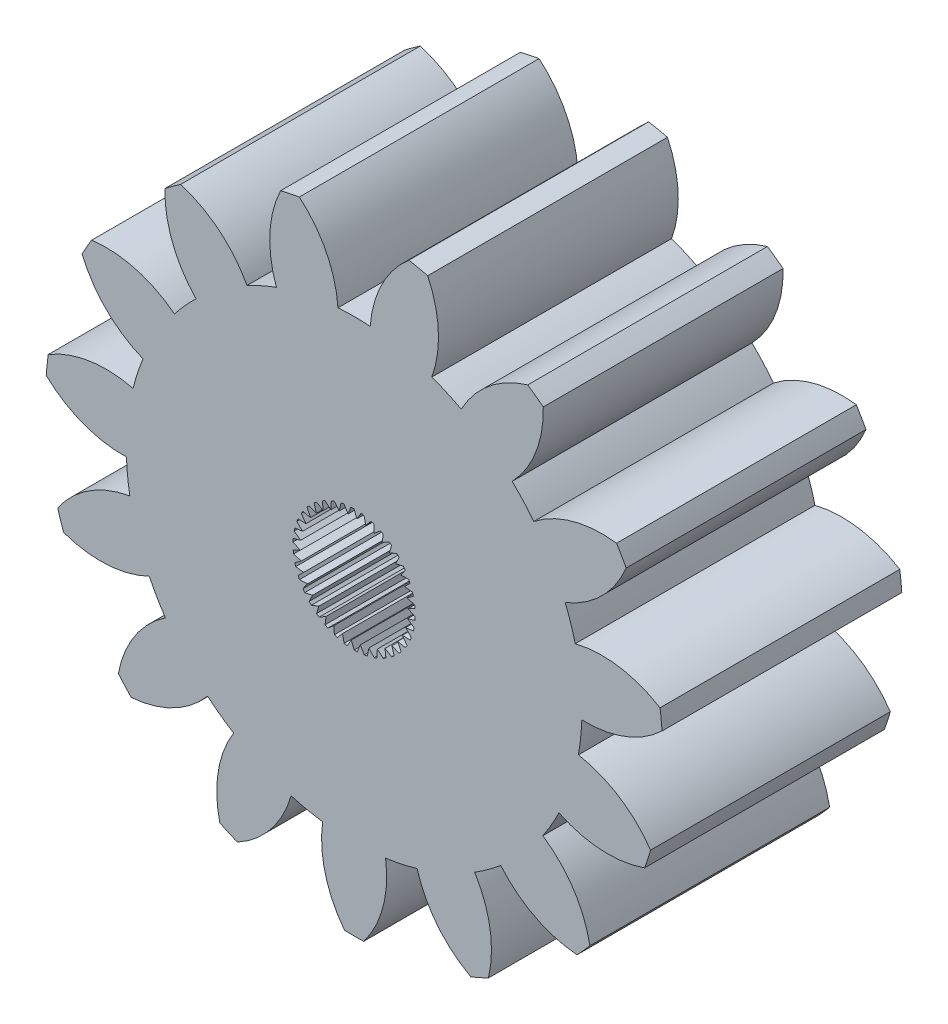
SolidWorks part; units mm, degrees
ref_plane "Front Plane" through (0, 0, 0) normal (0, 0, 1) x (1, 0, 0)
ref_plane "Top Plane" through (0, 0, 0) normal (0, 1, 0) x (1, 0, 0)
ref_plane "Right Plane" through (0, 0, 0) normal (1, 0, 0) x (0, 0, -1)
sketch "Sketch1" plane through (0, 0, 0) normal (0, 0, 1) x (1, 0, 0)
  circle A0 centre (0, 0) radius 70.548
extrude "Boss-Extrude1" add sketch "Sketch1" along normal blind 10
extrude "Cut-Extrude2" cut sketch "Sketch3" against normal through all contours A481 | A60 A239 A238 A237 A236 A235 A234 A233 A232 A231 A230 A229 A228 A227 A226 A225 A224 A223 A222 A221 A220 A219 A218 A217 A216 A215 A214 A213 A212 A211 A210 A209 A208 A207 A206 A205 A204 A203 A202 A201 A200 A199 A198 A197 A196 A195 A194 A193 A192 A191 region at (-345.5536, 6.387, 105.5946) region at (11.564, 6.387, 105.5946)
sketch "Sketch3" plane through (55.0256, -141.7184, 105.5946) normal (0, 0, 1) x (1, 0, 0)
  circle A60 centre (-43.4616, 148.1054) radius 367.5124
  arc A180 (-36.2212, 158.754) -> (-38.993, 156.4899) centre (-34.9077, 154.3174) ccw
  arc A181 (-38.993, 156.4899) -> (-40.2207, 157.0366) centre (-43.4616, 148.1054) ccw
  arc A182 (-40.2207, 157.0366) -> (-40.3928, 160.6114) centre (-44.5688, 158.6188) ccw
  arc A183 (-40.3928, 160.6114) -> (-41.1784, 160.7783) centre (-43.4616, 148.1054) ccw
  arc A184 (-41.1784, 160.7783) -> (-42.7896, 157.5826) centre (-38.1739, 157.2595) ccw
  arc A185 (-42.7896, 157.5826) -> (-44.1336, 157.5826) centre (-43.4616, 148.1054) ccw
  arc A186 (-44.1336, 157.5826) -> (-45.7448, 160.7783) centre (-48.7493, 157.2595) ccw
  arc A187 (-45.7448, 160.7783) -> (-46.5303, 160.6114) centre (-43.4616, 148.1054) ccw
  arc A188 (-46.5303, 160.6114) -> (-46.7024, 157.0366) centre (-42.3544, 158.6188) ccw
  arc A189 (-46.7024, 157.0366) -> (-47.9302, 156.4899) centre (-43.4616, 148.1054) ccw
  arc A190 (-47.9302, 156.4899) -> (-50.702, 158.754) centre (-52.0154, 154.3174) ccw
  arc A191 (-50.702, 158.754) -> (-51.3517, 158.282) centre (-43.4616, 148.1054) ccw
  arc A192 (-51.3517, 158.282) -> (-50.0549, 154.9462) centre (-46.7263, 158.1602) ccw
  arc A193 (-50.0549, 154.9462) -> (-50.9542, 153.9475) centre (-43.4616, 148.1054) ccw
  arc A194 (-50.9542, 153.9475) -> (-54.4072, 154.8885) centre (-53.8026, 150.3012) ccw
  arc A195 (-54.4072, 154.8885) -> (-54.8087, 154.193) centre (-43.4616, 148.1054) ccw
  arc A196 (-54.8087, 154.193) -> (-52.2673, 151.6731) centre (-50.5337, 155.963) ccw
  arc A197 (-52.2673, 151.6731) -> (-52.6826, 150.3949) centre (-43.4616, 148.1054) ccw
  arc A198 (-52.6826, 150.3949) -> (-56.2198, 149.8501) centre (-53.8016, 145.9053) ccw
  arc A199 (-56.2198, 149.8501) -> (-56.3038, 149.0514) centre (-43.4616, 148.1054) ccw
  arc A200 (-56.3038, 149.0514) -> (-52.9571, 147.783) centre (-53.1183, 152.4072) ccw
  arc A201 (-52.9571, 147.783) -> (-52.8166, 146.4464) centre (-43.4616, 148.1054) ccw
  arc A202 (-52.8166, 146.4464) -> (-55.8265, 144.51) centre (-52.0128, 141.8898) ccw
  arc A203 (-55.8265, 144.51) -> (-55.5783, 143.7462) centre (-43.4616, 148.1054) ccw
  arc A204 (-55.5783, 143.7462) -> (-52.0051, 143.9487) centre (-54.0331, 148.1076) ccw
  arc A205 (-52.0051, 143.9487) -> (-51.3331, 142.7848) centre (-43.4616, 148.1054) ccw
  arc A206 (-51.3331, 142.7848) -> (-53.2951, 139.7916) centre (-48.7454, 138.9491) ccw
  arc A207 (-53.2951, 139.7916) -> (-52.7577, 139.1948) centre (-43.4616, 148.1054) ccw
  arc A208 (-52.7577, 139.1948) -> (-49.5758, 140.8331) centre (-53.1201, 143.8076) ccw
  arc A209 (-49.5758, 140.8331) -> (-48.4885, 140.0432) centre (-43.4616, 148.1054) ccw
  arc A210 (-48.4885, 140.0432) -> (-49.0634, 136.5107) centre (-44.5644, 137.5915) ccw
  arc A211 (-49.0634, 136.5107) -> (-48.3298, 136.1841) centre (-43.4616, 148.1054) ccw
  arc A212 (-48.3298, 136.1841) -> (-46.0893, 138.975) centre (-50.537, 140.2507) ccw
  arc A213 (-46.0893, 138.975) -> (-44.7747, 138.6956) centre (-43.4616, 148.1054) ccw
  arc A214 (-44.7747, 138.6956) -> (-43.8631, 135.2346) centre (-40.1927, 138.0519) ccw
  arc A215 (-43.8631, 135.2346) -> (-43.06, 135.2346) centre (-43.4616, 148.1054) ccw
  arc A216 (-43.06, 135.2346) -> (-42.1484, 138.6956) centre (-46.7305, 138.0519) ccw
  arc A217 (-42.1484, 138.6956) -> (-40.8339, 138.975) centre (-43.4616, 148.1054) ccw
  arc A218 (-40.8339, 138.975) -> (-38.5934, 136.1841) centre (-36.3862, 140.2507) ccw
  arc A219 (-38.5934, 136.1841) -> (-37.8598, 136.5107) centre (-43.4616, 148.1054) ccw
  arc A220 (-37.8598, 136.5107) -> (-38.4347, 140.0432) centre (-42.3587, 137.5915) ccw
  arc A221 (-38.4347, 140.0432) -> (-37.3474, 140.8331) centre (-43.4616, 148.1054) ccw
  arc A222 (-37.3474, 140.8331) -> (-34.1654, 139.1948) centre (-33.8031, 143.8076) ccw
  arc A223 (-34.1654, 139.1948) -> (-33.6281, 139.7916) centre (-43.4616, 148.1054) ccw
  arc A224 (-33.6281, 139.7916) -> (-35.5901, 142.7848) centre (-38.1777, 138.9491) ccw
  arc A225 (-35.5901, 142.7848) -> (-34.9181, 143.9487) centre (-43.4616, 148.1054) ccw
  arc A226 (-34.9181, 143.9487) -> (-31.3449, 143.7462) centre (-32.89, 148.1076) ccw
  arc A227 (-31.3449, 143.7462) -> (-31.0967, 144.51) centre (-43.4616, 148.1054) ccw
  arc A228 (-31.0967, 144.51) -> (-34.1065, 146.4464) centre (-34.9103, 141.8898) ccw
  arc A229 (-34.1065, 146.4464) -> (-33.966, 147.783) centre (-43.4616, 148.1054) ccw
  arc A230 (-33.966, 147.783) -> (-30.6194, 149.0514) centre (-33.8049, 152.4072) ccw
  arc A231 (-30.6194, 149.0514) -> (-30.7033, 149.8501) centre (-43.4616, 148.1054) ccw
  arc A232 (-30.7033, 149.8501) -> (-34.2406, 150.3949) centre (-33.1215, 145.9053) ccw
  arc A233 (-34.2406, 150.3949) -> (-34.6559, 151.6731) centre (-43.4616, 148.1054) ccw
  arc A234 (-34.6559, 151.6731) -> (-32.1144, 154.193) centre (-36.3895, 155.963) ccw
  arc A235 (-32.1144, 154.193) -> (-32.516, 154.8885) centre (-43.4616, 148.1054) ccw
  arc A236 (-32.516, 154.8885) -> (-35.969, 153.9475) centre (-33.1206, 150.3012) ccw
  arc A237 (-35.969, 153.9475) -> (-36.8683, 154.9462) centre (-43.4616, 148.1054) ccw
  arc A238 (-36.8683, 154.9462) -> (-35.5715, 158.282) centre (-40.1969, 158.1602) ccw
  arc A239 (-35.5715, 158.282) -> (-36.2212, 158.754) centre (-43.4616, 148.1054) ccw
  circle A481 centre (-43.4616, 148.1054) radius 2.25
sketch "Sketch4" plane through (0, 0, 10) normal (0, 0, 1) x (1, 0, 0)
  line L0 (9.4595, 5.591) -> (9.128, 5.6333)
  line L1 (9.4595, 5.591) -> (9.2295, 5.361)
  line L2 (9.3572, 5.9482) -> (9.0925, 5.7592)
  line L3 (9.3572, 5.9482) -> (9.0371, 6.0445)
  line L4 (9.3151, 6.3174) -> (9.0229, 6.1746)
  line L5 (9.3151, 6.3174) -> (9.0152, 6.4651)
  line L6 (9.3343, 6.6885) -> (9.0226, 6.5957)
  line L7 (9.3343, 6.6885) -> (9.0628, 6.8836)
  line L8 (9.4144, 7.0514) -> (9.0916, 7.0112)
  line L9 (9.4144, 7.0514) -> (9.1787, 7.2885)
  line L10 (9.5531, 7.3962) -> (9.2281, 7.4096)
  line L11 (9.5531, 7.3962) -> (9.3596, 7.6688)
  line L12 (9.7466, 7.7134) -> (9.4282, 7.7802)
  line L13 (9.7466, 7.7134) -> (9.6007, 8.0142)
  line L14 (9.9897, 7.9945) -> (9.6867, 8.1127)
  line L15 (9.9897, 7.9945) -> (9.8953, 8.3151)
  line L16 (10.2758, 8.2317) -> (9.9963, 8.3982)
  line L17 (10.2758, 8.2317) -> (10.2354, 8.5635)
  line L18 (10.5969, 8.4186) -> (10.3487, 8.6288)
  line L19 (10.5969, 8.4186) -> (10.6117, 8.7525)
  line L20 (10.9445, 8.55) -> (10.7343, 8.7982)
  line L21 (10.9445, 8.55) -> (11.0141, 8.877)
  line L22 (11.309, 8.6225) -> (11.1425, 8.9019)
  line L23 (11.309, 8.6225) -> (11.4314, 8.9335)
  line L24 (11.6804, 8.634) -> (11.5622, 8.937)
  line L25 (11.6804, 8.634) -> (11.8524, 8.9206)
  line L26 (12.0487, 8.5842) -> (11.9819, 8.9025)
  line L27 (12.0487, 8.5842) -> (12.2655, 8.8386)
  line L28 (12.4037, 8.4744) -> (12.3903, 8.7994)
  line L29 (12.4037, 8.4744) -> (12.6594, 8.6897)
  line L30 (12.7358, 8.3078) -> (12.7761, 8.6305)
  line L31 (12.7358, 8.3078) -> (13.0235, 8.478)
  line L32 (13.036, 8.0887) -> (13.1288, 8.4004)
  line L33 (13.036, 8.0887) -> (13.3478, 8.2093)
  line L34 (13.296, 7.8232) -> (13.4389, 8.1154)
  line L35 (13.296, 7.8232) -> (13.6234, 7.8908)
  line L36 (13.5088, 7.5185) -> (13.6978, 7.7833)
  line L37 (13.5088, 7.5185) -> (13.8428, 7.5314)
  line L38 (13.6685, 7.183) -> (13.8985, 7.413)
  line L39 (13.6685, 7.183) -> (14.0001, 7.1407)
  line L40 (13.7708, 6.8258) -> (14.0355, 7.0148)
  line L41 (13.7708, 6.8258) -> (14.0909, 6.7294)
  line L42 (13.813, 6.4566) -> (14.1052, 6.5994)
  line L43 (13.813, 6.4566) -> (14.1128, 6.3089)
  line L44 (13.7937, 6.0854) -> (14.1055, 6.1783)
  line L45 (13.7937, 6.0854) -> (14.0652, 5.8904)
  line L46 (13.7137, 5.7226) -> (14.0364, 5.7628)
  line L47 (13.7137, 5.7226) -> (13.9494, 5.4855)
  line L48 (13.575, 5.3778) -> (13.9, 5.3644)
  line L49 (13.575, 5.3778) -> (13.7684, 5.1052)
  line L50 (13.3815, 5.0606) -> (13.6998, 4.9938)
  line L51 (13.3815, 5.0606) -> (13.5274, 4.7598)
  line L52 (13.1384, 4.7795) -> (13.4414, 4.6613)
  line L53 (13.1384, 4.7795) -> (13.2328, 4.4589)
  line L54 (12.8523, 4.5423) -> (13.1317, 4.3758)
  line L55 (12.8523, 4.5423) -> (12.8927, 4.2105)
  line L56 (12.5311, 4.3554) -> (12.7793, 4.1452)
  line L57 (12.5311, 4.3554) -> (12.5163, 4.0215)
  line L58 (12.1835, 4.224) -> (12.3938, 3.9758)
  line L59 (12.1835, 4.224) -> (12.114, 3.897)
  line L60 (11.8191, 4.1515) -> (11.9856, 3.8721)
  line L61 (11.8191, 4.1515) -> (11.6966, 3.8404)
  line L62 (11.4476, 4.14) -> (11.5659, 3.837)
  line L63 (11.4476, 4.14) -> (11.2757, 3.8534)
  line L64 (11.0794, 4.1898) -> (11.1461, 3.8715)
  line L65 (11.0794, 4.1898) -> (10.8626, 3.9354)
  line L66 (10.7243, 4.2995) -> (10.7378, 3.9746)
  line L67 (10.7243, 4.2995) -> (10.4686, 4.0843)
  line L68 (10.3922, 4.4662) -> (10.352, 4.1435)
  line L69 (10.3922, 4.4662) -> (10.1046, 4.296)
  line L70 (10.092, 4.6853) -> (9.9992, 4.3736)
  line L71 (10.092, 4.6853) -> (9.7803, 4.5647)
  line L72 (9.832, 4.9508) -> (9.6892, 4.6586)
  line L73 (9.832, 4.9508) -> (9.5047, 4.8831)
  line L74 (9.6193, 5.2555) -> (9.4303, 4.9907)
  line L75 (9.6193, 5.2555) -> (9.2852, 5.2426)
  circle A2 centre (11.564, 6.387) radius 2.55
  circle A3 centre (11.564, 6.387) radius 2.55
  point P123 (11.564, 6.387)
  dimension "D1" = 0.3
  dimension "D3" = 38
extrude "Cut-Extrude4" cut sketch "Sketch4" against normal blind 10 contours L42 A3 L41 L40 L39 L38 L37 L36 L35 L34 L33 L32 L31 L30 L29 L28 L27 L26 L25 L24 L23 L22 L21 L20 L19 L18 L17 L16 L15 L14 L13 L12 L11 L10 L9 region at (11.564, 6.387, 10)
